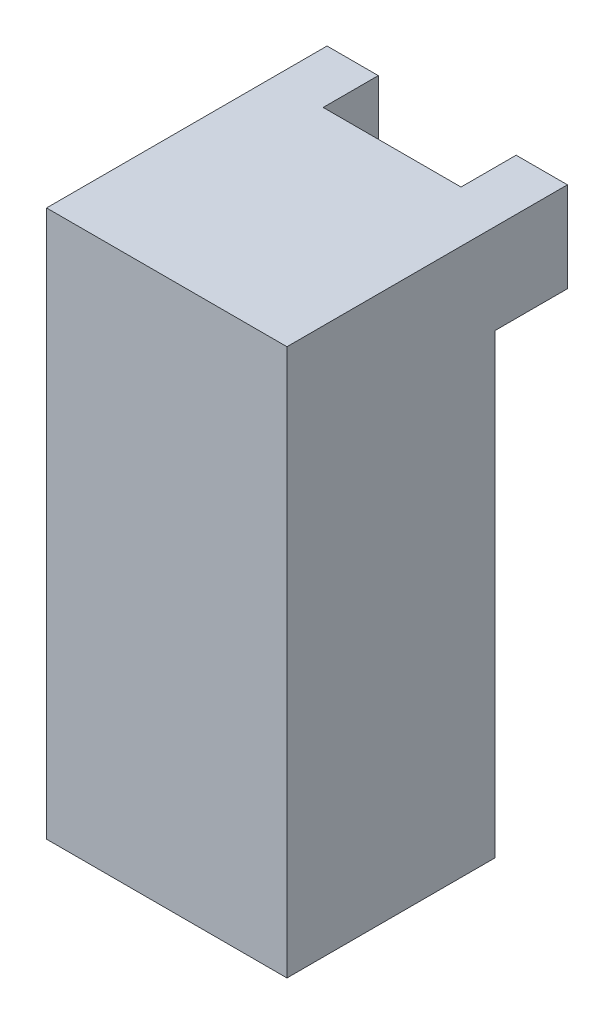
SolidWorks part; units mm, degrees
ref_plane "Front Plane" through (0, 0, 0) normal (0, 0, 1) x (1, 0, 0)
ref_plane "Top Plane" through (0, 0, 0) normal (0, 1, 0) x (1, 0, 0)
ref_plane "Right Plane" through (0, 0, 0) normal (1, 0, 0) x (0, 0, -1)
sketch "Sketch1" plane through (0, 0, 0) normal (0, 1, 0) x (1, 0, 0)
  line L1 (-2.79, -2.415) -> (2.79, -2.415)
  line L2 (-2.79, -2.415) -> (-2.79, 2.415)
  line L3 (-2.79, 2.415) -> (2.79, 2.415)
  line L4 (2.79, -2.415) -> (2.79, 2.415)
  line L5 (-2.79, -2.415) -> (2.79, 2.415) construction
  line L6 (-2.79, 2.415) -> (2.79, -2.415) construction
  point P0 (0, 0)
  dimension "D1" = 5.58
  dimension "D2" = 4.83
extrude "Boss-Extrude1" add sketch "Sketch1" along normal mid plane 12.69
sketch "Sketch2" plane through (0, 6.345, 0) normal (0, 1, 0) x (1, 0, 0)
  line L0 (-2.79, -2.415) -> (2.79, -2.415) construction
  line L1 (-2.79, 2.415) -> (-1.6, 2.415)
  line L2 (-2.79, 2.415) -> (-2.79, 4.095)
  line L3 (-2.79, 4.095) -> (-1.6, 4.095)
  line L4 (-1.6, 2.415) -> (-1.6, 4.095)
  line L5 (2.79, 2.415) -> (1.6, 2.415)
  line L6 (2.79, 2.415) -> (2.79, 4.095)
  line L7 (2.79, 4.095) -> (1.6, 4.095)
  line L8 (1.6, 2.415) -> (1.6, 4.095)
  dimension "D1" = 6.51
  dimension "D2" = 3.2
extrude "Boss-Extrude2" add sketch "Sketch2" against normal blind 2.09
sketch "Sketch4" plane through (0, 6.345, 0) normal (0, 1, 0) x (1, 0, 0)
  line L0 (-1.6, 2.415) -> (-1.6, 4.095) construction
  line L1 (-1.6, 2.815) -> (1.6, 2.815)
  line L2 (-1.6, 2.815) -> (-1.6, 2.415)
  line L3 (-1.6, 2.415) -> (1.6, 2.415)
  line L4 (1.6, 2.815) -> (1.6, 2.415)
  dimension "D1" = 0.4
extrude "Boss-Extrude3" add sketch "Sketch4" against normal up to surface (2.09 mm away) up to face at (2.195, 4.255, -3.255)
